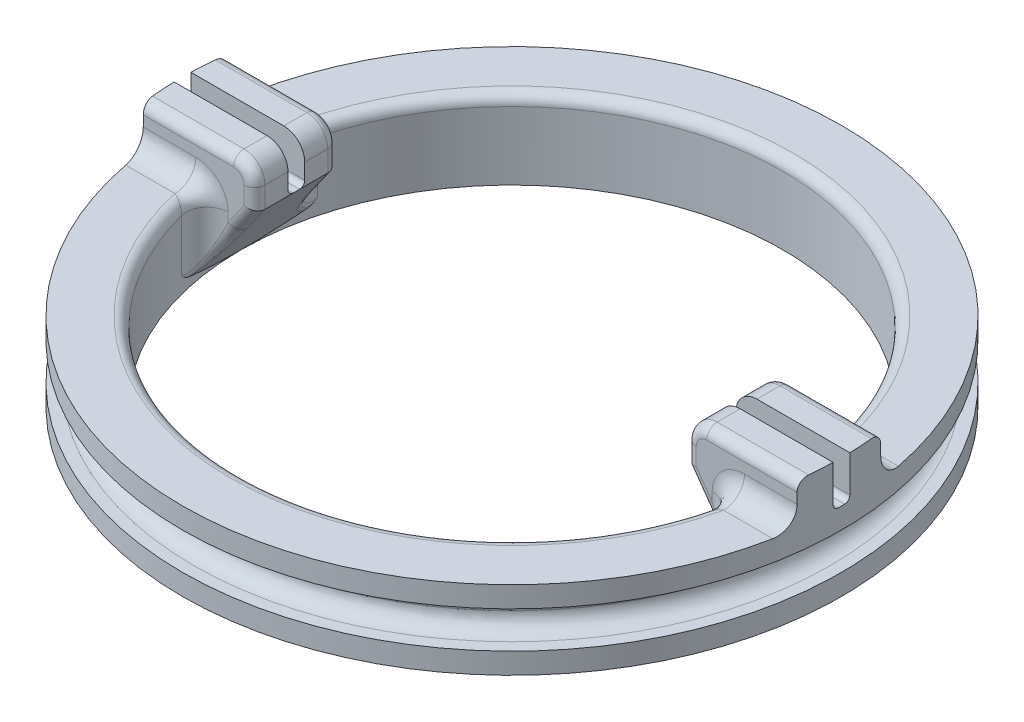
SolidWorks part; units mm, degrees
ref_plane "Front Plane" through (0, 0, 0) normal (0, 0, 1) x (1, 0, 0)
ref_plane "Top Plane" through (0, 0, 0) normal (0, 1, 0) x (1, 0, 0)
ref_plane "Right Plane" through (0, 0, 0) normal (1, 0, 0) x (0, 0, -1)
sketch "Sketch1" plane through (0, 0, 0) normal (0, 0, 1) x (1, 0, 0)
  line L2 (-31.5, 0) -> (-31.5, -2)
  line L3 (-31.5, -2) -> (-28.9, -2)
  line L4 (-28.9, -2) -> (-28.9, -5.5)
  line L5 (-28.9, -5.5) -> (-31.5, -5.5)
  line L6 (-31.5, -5.5) -> (-31.5, -7.5)
  line L7 (-31.5, -7.5) -> (-25.9, -7.5)
  line L16 (0, 57.5161) -> (0, -30.951) construction
  line L17 (-25.9, 0) -> (-25.9, -7.5)
  line L18 (-31.5, 0) -> (-25.9, 0)
  dimension "D2" = 2
  dimension "D3" = 25.9
  dimension "D4" = 28.9
  dimension "D5" = 31.5
  dimension "D9" = 2
  dimension "D12" = 3.5
revolve "Revolve1" add sketch "Sketch1" angle 360 about L16
chamfer "Chamfer1" distance 1.5 angle 60 1 edges at (0, -2, 28.9) first distance on face at (0, -5.5, 28.9)
fillet "Fillet7" radius 1.5 1 edges at (0, -5.5, 28.9)
fillet "Fillet8" radius 0.8 1 edges at (0, -3.5, -28.9)
sketch "Sketch2" plane through (0, 0, 0) normal (0, 0, 1) x (1, 0, 0)
  line L0 (-32.6107, 0) -> (-32.6107, 4)
  line L1 (31.5, 0) -> (-31.5, 0) construction
  line L2 (-32.6107, 4) -> (-20.6107, 4)
  line L3 (-20.6107, 4) -> (-20.6107, 0)
  line L4 (-31.5, -7.5) -> (31.5, -7.5) construction
  line L6 (-25.9, -7.5) -> (-25.9, 0)
  line L7 (-25.9, 0) -> (-32.6107, 0)
  line L8 (-25.9, 0) -> (-25.9, -7.5) construction
  line L16 (0, 15.2417) -> (0, -15.3534) construction
  line L23 (25.9, 0) -> (32.6107, 0)
  line L24 (25.9, -7.5) -> (25.9, 0)
  line L25 (20.6107, 0) -> (25.9, -7.5)
  line L26 (20.6107, 4) -> (20.6107, 0)
  line L27 (32.6107, 4) -> (20.6107, 4)
  line L28 (32.6107, 0) -> (32.6107, 4)
  line L29 (-20.6107, 0) -> (-25.9, -7.5)
  circle A1 centre (27.5, 6) radius 1.25 construction
  dimension "D1" = 4
  dimension "D3" = 12
  dimension "D6" = 4
extrude "Boss-Extrude1" add sketch "Sketch2" along normal blind 4 and the other way blind 4
sketch "Sketch3" plane through (0, 0, 0) normal (0, 1, 0) x (1, 0, 0)
  circle A0 centre (0, 0) radius 31.5
  circle A1 centre (0, 0) radius 31.5 construction
extrude "Cut-Extrude1" cut sketch "Sketch3" along normal through all flip side to cut
sketch "Sketch4" plane through (0, 0, 0) normal (1, 0, 0) x (0, 0, -1)
  line L0 (0.8, 6) -> (0.8, 0)
  line L1 (0.8, 0) -> (-0.8, 0)
  line L2 (-0.8, 0) -> (-0.8, 6)
  line L3 (-0.8, 6) -> (0.8, 6)
  point P5 (0, 0)
  point P7 (0, 0)
  dimension "D1" = 1.6
  dimension "D2" = 6
extrude "Cut-Extrude2" cut sketch "Sketch4" against normal through all both and the other way through all
fillet "Fillet9" radius 1 2 edges at (0, 0, 25.9) (0, 0, -25.9)
fillet "Fillet11" radius 2 16 edges at (25.5893, -4.0297, -4) (25.9635, -0.2236, -4) (-25.5893, -4.0297, -4) (-25.8065, -0.3809, -4) (25.5893, -4.0297, 4) (25.8065, -0.3809, 4) (-25.5893, -4.0297, 4) (-25.9635, -0.2236, 4) (20.6107, 4, -2.4) (20.6107, 4, 2.4) (-20.6107, 4, -2.4) (-20.6107, 4, 2.4) (28.923, 0, -4) (-28.923, 0, -4) (28.923, 0, 4) (-28.923, 0, 4)
fillet "Fillet12" radius 0.5 4 edges at (26.0503, 0, -0.8) (26.0503, 0, 0.8) (-26.0503, 0, 0.8) (-26.0503, 0, -0.8)
fillet "Fillet13" radius 1 20 edges at (24.7164, -5.8217, -4.7761) (20.6107, 1, -4) (21.1965, 3.4142, -4) (24.7164, -5.8217, 4.7761) (20.6107, 1, 4) (21.1965, 3.4142, 4) (-24.7164, -5.8217, -4.7761) (-20.6107, 1, -4) (-21.1965, 3.4142, -4) (-24.7164, -5.8217, 4.7761) (-20.6107, 1, 4) (-21.1965, 3.4142, 4) (21.8727, -1.7894, -4) (26.9279, 4, -4) (21.8727, -1.7894, 4) (26.9279, 4, 4) (-21.8727, -1.7894, -4) (-26.9279, 4, -4) (-21.8727, -1.7894, 4) (-26.9279, 4, 4)
